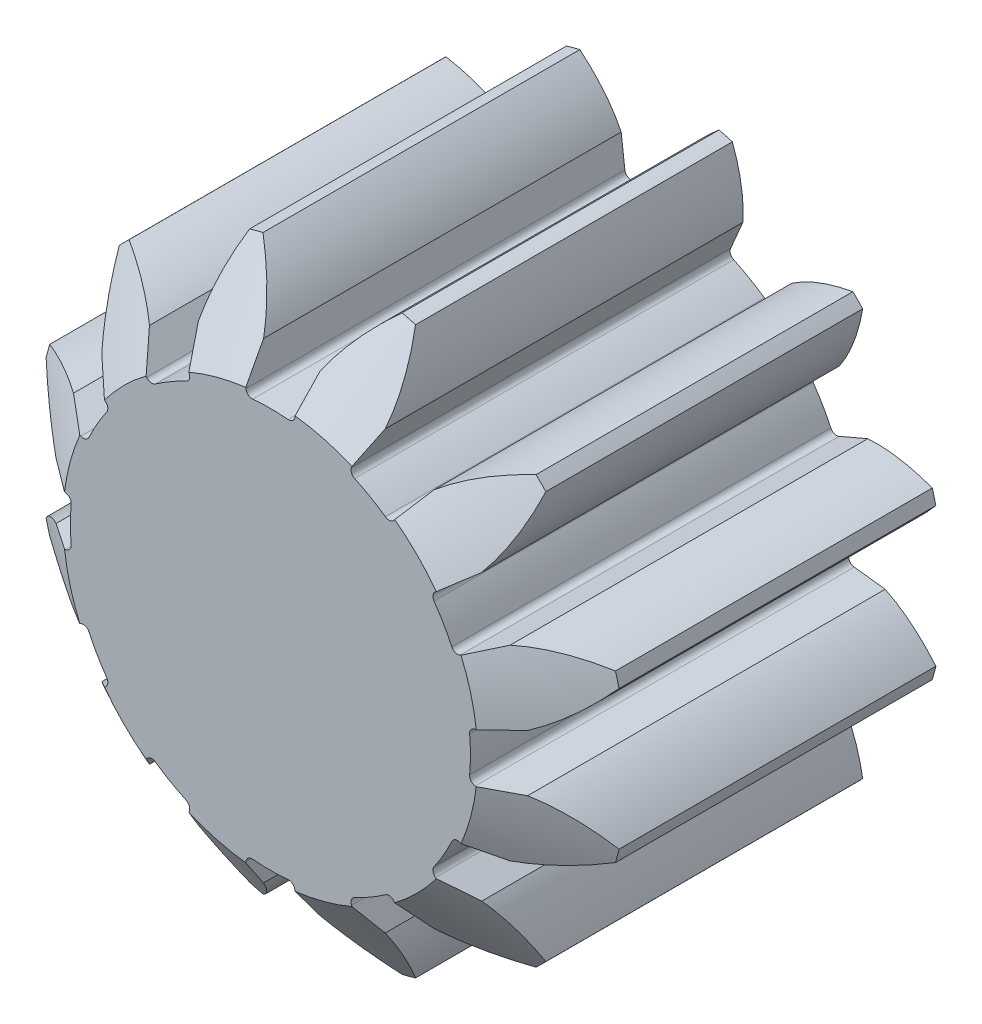
SolidWorks part; units mm, degrees
ref_plane "前视基准面" through (0, 0, 0) normal (0, 0, 1) x (1, 0, 0)
ref_plane "上视基准面" through (0, 0, 0) normal (0, 1, 0) x (1, 0, 0)
ref_plane "右视基准面" through (0, 0, 0) normal (1, 0, 0) x (0, 0, -1)
sketch "直齿轮" plane through (0, 0, 0) normal (0, 0, 1) x (1, 0, 0)
  line L0 (0, 14) -> (0, -14) construction
  line L1 (0, 0) -> (-1.3412, 11.1963)
  line L2 (0, 0) -> (1.3412, 11.1963)
  circle A0 centre (0, 0) radius 14
  arc A1 (1.5663, 11.8973) -> (-1.5663, 11.8973) centre (0, 0) ccw
  circle A2 centre (0, 0) radius 9.5
  circle A3 centre (0, 0) radius 11.2763
  spline S0 degree 4 poles (0.5104, 10.8373) (0.5087, 10.8802) (0.5014, 10.9656) (0.4731, 11.1267) (0.4127, 11.3596) (0.277, 11.753) (-0.0082, 12.3501) (-0.4967, 13.0965) (-1.3216, 14.0307) (-2.4412, 14.9688) (-3.8063, 15.812) (-5.3884, 16.5087) (-7.0436, 17.0043) (-8.7436, 17.3098) (-10.5508, 17.442) (-12.7938, 17.3717) (-15.4399, 16.9453) (-18.4103, 16.0061) (-21.5089, 14.4656) (-24.3525, 12.4965) (-26.9034, 10.1625) (-28.856, 7.8529) (-30.319, 5.7166) (-31.3943, 3.848) (-32.1672, 2.306) (-32.8522, 0.7235) (-33.449, -0.8951) (-34.0845, -2.9542) (-34.5731, -5.0569) (-34.8816, -6.9706) (-35.0445, -8.5826) (-35.1063, -9.4362) (-35.138, -10.019) (-35.1582, -10.475) (-35.1745, -11.1216) (-35.1793, -11.604) (-35.1756, -12.3979) (-35.1555, -13.0081) (-35.1236, -13.7549) (-35.0774, -14.4165) (-35.0185, -15.1311) (-34.9461, -15.8066) (-34.8823, -16.3369) (-34.8352, -16.674) (-34.8107, -16.8492) knots 0 0 0 0 0 0.002802 0.005604 0.010661 0.015718 0.02996 0.048734 0.068727 0.096889 0.125051 0.153212 0.181374 0.209535 0.237696 0.271429 0.327752 0.384075 0.440398 0.496721 0.553044 0.609367 0.637529 0.66569 0.693852 0.722013 0.750174 0.778336 0.834659 0.86282 0.876901 0.883942 0.890982 0.900036 0.909091 0.920455 0.931818 0.943182 0.954545 0.965909 0.977273 0.988636 1 1 1 1 1 construction
  spline S1 degree 4 poles (-1.3412, 11.1963) (-1.4143, 11.3505) (-1.6248, 11.7455) (-2.0413, 12.3619) (-2.8158, 13.2253) (-3.8997, 14.1193) (-5.2192, 14.9202) (-6.7463, 15.5786) (-8.3421, 16.0429) (-9.9797, 16.3241) (-11.7191, 16.4378) (-13.8762, 16.3534) (-16.4184, 15.9235) (-19.2687, 14.9979) (-22.2378, 13.4928) (-24.9584, 11.5775) (-27.3948, 9.3133) (-29.2558, 7.077) (-30.6471, 5.0111) (-31.6676, 3.2056) (-32.3996, 1.7166) (-33.0467, 0.1892) (-33.6086, -1.3723) (-34.2045, -3.3577) (-34.6589, -5.384) (-34.9413, -7.2271) (-35.086, -8.779) (-35.1391, -9.6005) (-35.1652, -10.1614) (-35.1812, -10.6002) (-35.1921, -11.2223) (-35.1931, -11.6864) (-35.1836, -12.45) (-35.1626, -12.9672) (-35.1409, -13.4074) (-35.1253, -13.6673) (-35.1196, -13.7558) knots 0.018362 0.018362 0.018362 0.018362 0.018362 0.02996 0.048734 0.068727 0.096889 0.125051 0.153212 0.181374 0.209535 0.237696 0.271429 0.327752 0.384075 0.440398 0.496721 0.553044 0.609367 0.637529 0.66569 0.693852 0.722013 0.750174 0.778336 0.834659 0.86282 0.876901 0.883942 0.890982 0.900036 0.909091 0.920455 0.931818 0.943182 0.949152 0.949152 0.949152 0.949152 0.949152
  spline S2 degree 4 poles (-0.5104, 10.8373) (-0.5087, 10.8802) (-0.5014, 10.9656) (-0.4731, 11.1267) (-0.4127, 11.3596) (-0.277, 11.753) (0.0082, 12.3501) (0.4967, 13.0965) (1.3216, 14.0307) (2.4412, 14.9688) (3.8063, 15.812) (5.3884, 16.5087) (7.0436, 17.0043) (8.7436, 17.3098) (10.5508, 17.442) (12.7938, 17.3717) (15.4399, 16.9453) (18.4103, 16.0061) (21.5089, 14.4656) (24.3525, 12.4965) (26.9034, 10.1625) (28.856, 7.8529) (30.319, 5.7166) (31.3943, 3.848) (32.1672, 2.306) (32.8522, 0.7235) (33.449, -0.8951) (34.0845, -2.9542) (34.5731, -5.0569) (34.8816, -6.9706) (35.0445, -8.5826) (35.1063, -9.4362) (35.138, -10.019) (35.1582, -10.475) (35.1745, -11.1216) (35.1793, -11.604) (35.1756, -12.3979) (35.1555, -13.0081) (35.1236, -13.7549) (35.0774, -14.4165) (35.0185, -15.1311) (34.9461, -15.8066) (34.8823, -16.3369) (34.8352, -16.674) (34.8107, -16.8492) knots 0 0 0 0 0 0.002802 0.005604 0.010661 0.015718 0.02996 0.048734 0.068727 0.096889 0.125051 0.153212 0.181374 0.209535 0.237696 0.271429 0.327752 0.384075 0.440398 0.496721 0.553044 0.609367 0.637529 0.66569 0.693852 0.722013 0.750174 0.778336 0.834659 0.86282 0.876901 0.883942 0.890982 0.900036 0.909091 0.920455 0.931818 0.943182 0.954545 0.965909 0.977273 0.988636 1 1 1 1 1 construction
  spline S3 degree 4 poles (1.3412, 11.1963) (1.4143, 11.3505) (1.6248, 11.7455) (2.0413, 12.3619) (2.8158, 13.2253) (3.8997, 14.1193) (5.2192, 14.9202) (6.7463, 15.5786) (8.3421, 16.0429) (9.9797, 16.3241) (11.7191, 16.4378) (13.8762, 16.3534) (16.4184, 15.9235) (19.2687, 14.9979) (22.2378, 13.4928) (24.9584, 11.5775) (27.3948, 9.3133) (29.2558, 7.077) (30.6471, 5.0111) (31.6676, 3.2056) (32.3996, 1.7166) (33.0467, 0.1892) (33.6086, -1.3723) (34.2045, -3.3577) (34.6589, -5.384) (34.9413, -7.2271) (35.086, -8.779) (35.1391, -9.6005) (35.1652, -10.1614) (35.1812, -10.6002) (35.1921, -11.2223) (35.1931, -11.6864) (35.1836, -12.45) (35.1626, -12.9672) (35.1409, -13.4074) (35.1253, -13.6673) (35.1196, -13.7558) knots 0.018362 0.018362 0.018362 0.018362 0.018362 0.02996 0.048734 0.068727 0.096889 0.125051 0.153212 0.181374 0.209535 0.237696 0.271429 0.327752 0.384075 0.440398 0.496721 0.553044 0.609367 0.637529 0.66569 0.693852 0.722013 0.750174 0.778336 0.834659 0.86282 0.876901 0.883942 0.890982 0.900036 0.909091 0.920455 0.931818 0.943182 0.949152 0.949152 0.949152 0.949152 0.949152
  dimension "齿顶圆" = 28
  dimension "分度圆" = 24
  dimension "齿根圆" = 19
  dimension "基圆直径" = 22.5526
  dimension "D1" = 3.1416
extrude "齿轮毛坯" add sketch "直齿轮" along normal mid plane 22 contours A0
chamfer "轮齿倒角" distance 1 angle 45 2 edges at (14, 0, -11) (14, 0, 11)
sketch "草图2" plane through (0, 0, 0) normal (0, 0, 1) x (1, 0, 0)
  line L0 (0, 0) -> (-1.3412, 11.1963) construction
  line L1 (0, 0) -> (1.3412, 11.1963) construction
  line L2 (0, 0) -> (-1.3412, 11.1963)
  line L3 (0, 0) -> (1.3412, 11.1963)
  circle A0 centre (0, 0) radius 14 construction
  circle A1 centre (0, 0) radius 14
  circle A2 centre (0, 0) radius 9.5 construction
  circle A3 centre (0, 0) radius 9.5
  spline S0 degree 4 poles (-1000.3168, -32.7859) (-34.8369, -15.4454) (0.1123, -1.0379) (1.6887, 8.2033) (-2.8158, 13.2253) (-3.8997, 14.1193) (-5.2192, 14.9202) (-6.7463, 15.5786) (-8.3421, 16.0429) (-9.9797, 16.3241) (-11.7191, 16.4378) (-13.8762, 16.3534) (-16.4184, 15.9235) (-19.2687, 14.9979) (-22.2378, 13.4928) (-24.9584, 11.5775) (-27.3948, 9.3133) (-29.2558, 7.077) (-30.6471, 5.0111) (-31.6676, 3.2056) (-32.3996, 1.7166) (-33.0467, 0.1892) (-33.6086, -1.3723) (-34.2045, -3.3577) (-34.6589, -5.384) (-34.9413, -7.2271) (-35.086, -8.779) (-35.1391, -9.6005) (-35.1652, -10.1614) (-35.1812, -10.6002) (-35.1921, -11.2223) (-35.1931, -11.6864) (-35.1836, -12.45) (-35.0654, -15.3572) (-34.587, -21.9927) (-33.6323, 18.5401) (-36.6239, -1013.6039) knots -0.359858 -0.359858 -0.359858 -0.359858 -0.359858 0.02996 0.048734 0.068727 0.096889 0.125051 0.153212 0.181374 0.209535 0.237696 0.271429 0.327752 0.384075 0.440398 0.496721 0.553044 0.609367 0.637529 0.66569 0.693852 0.722013 0.750174 0.778336 0.834659 0.86282 0.876901 0.883942 0.890982 0.900036 0.909091 0.920455 0.931818 0.943182 1.134286 1.134286 1.134286 1.134286 1.134286 only from (-1.3412, 11.1963) to (-35.1196, -13.7558) construction
  spline S1 degree 4 poles (-1.3412, 11.1963) (-1.4143, 11.3505) (-1.6248, 11.7455) (-2.0413, 12.3619) (-2.8158, 13.2253) (-3.8997, 14.1193) (-5.2192, 14.9202) (-6.7463, 15.5786) (-8.3421, 16.0429) (-9.9797, 16.3241) (-11.7191, 16.4378) (-13.8762, 16.3534) (-16.4184, 15.9235) (-19.2687, 14.9979) (-22.2378, 13.4928) (-24.9584, 11.5775) (-27.3948, 9.3133) (-29.2558, 7.077) (-30.6471, 5.0111) (-31.6676, 3.2056) (-32.3996, 1.7166) (-33.0467, 0.1892) (-33.6086, -1.3723) (-34.2045, -3.3577) (-34.6589, -5.384) (-34.9413, -7.2271) (-35.086, -8.779) (-35.1391, -9.6005) (-35.1652, -10.1614) (-35.1812, -10.6002) (-35.1921, -11.2223) (-35.1931, -11.6864) (-35.1836, -12.45) (-35.1626, -12.9672) (-35.1409, -13.4074) (-35.1253, -13.6673) (-35.1196, -13.7558) knots 0.018362 0.018362 0.018362 0.018362 0.018362 0.02996 0.048734 0.068727 0.096889 0.125051 0.153212 0.181374 0.209535 0.237696 0.271429 0.327752 0.384075 0.440398 0.496721 0.553044 0.609367 0.637529 0.66569 0.693852 0.722013 0.750174 0.778336 0.834659 0.86282 0.876901 0.883942 0.890982 0.900036 0.909091 0.920455 0.931818 0.943182 0.949152 0.949152 0.949152 0.949152 0.949152
  spline S2 degree 4 poles (1000.3168, -32.7859) (34.8369, -15.4454) (-0.1123, -1.0379) (-1.6887, 8.2033) (2.8158, 13.2253) (3.8997, 14.1193) (5.2192, 14.9202) (6.7463, 15.5786) (8.3421, 16.0429) (9.9797, 16.3241) (11.7191, 16.4378) (13.8762, 16.3534) (16.4184, 15.9235) (19.2687, 14.9979) (22.2378, 13.4928) (24.9584, 11.5775) (27.3948, 9.3133) (29.2558, 7.077) (30.6471, 5.0111) (31.6676, 3.2056) (32.3996, 1.7166) (33.0467, 0.1892) (33.6086, -1.3723) (34.2045, -3.3577) (34.6589, -5.384) (34.9413, -7.2271) (35.086, -8.779) (35.1391, -9.6005) (35.1652, -10.1614) (35.1812, -10.6002) (35.1921, -11.2223) (35.1931, -11.6864) (35.1836, -12.45) (35.0654, -15.3572) (34.587, -21.9927) (33.6323, 18.5401) (36.6239, -1013.6039) knots -0.359858 -0.359858 -0.359858 -0.359858 -0.359858 0.02996 0.048734 0.068727 0.096889 0.125051 0.153212 0.181374 0.209535 0.237696 0.271429 0.327752 0.384075 0.440398 0.496721 0.553044 0.609367 0.637529 0.66569 0.693852 0.722013 0.750174 0.778336 0.834659 0.86282 0.876901 0.883942 0.890982 0.900036 0.909091 0.920455 0.931818 0.943182 1.134286 1.134286 1.134286 1.134286 1.134286 only from (1.3412, 11.1963) to (35.1196, -13.7558) construction
  spline S3 degree 4 poles (1.3412, 11.1963) (1.4143, 11.3505) (1.6248, 11.7455) (2.0413, 12.3619) (2.8158, 13.2253) (3.8997, 14.1193) (5.2192, 14.9202) (6.7463, 15.5786) (8.3421, 16.0429) (9.9797, 16.3241) (11.7191, 16.4378) (13.8762, 16.3534) (16.4184, 15.9235) (19.2687, 14.9979) (22.2378, 13.4928) (24.9584, 11.5775) (27.3948, 9.3133) (29.2558, 7.077) (30.6471, 5.0111) (31.6676, 3.2056) (32.3996, 1.7166) (33.0467, 0.1892) (33.6086, -1.3723) (34.2045, -3.3577) (34.6589, -5.384) (34.9413, -7.2271) (35.086, -8.779) (35.1391, -9.6005) (35.1652, -10.1614) (35.1812, -10.6002) (35.1921, -11.2223) (35.1931, -11.6864) (35.1836, -12.45) (35.1626, -12.9672) (35.1409, -13.4074) (35.1253, -13.6673) (35.1196, -13.7558) knots 0.018362 0.018362 0.018362 0.018362 0.018362 0.02996 0.048734 0.068727 0.096889 0.125051 0.153212 0.181374 0.209535 0.237696 0.271429 0.327752 0.384075 0.440398 0.496721 0.553044 0.609367 0.637529 0.66569 0.693852 0.722013 0.750174 0.778336 0.834659 0.86282 0.876901 0.883942 0.890982 0.900036 0.909091 0.920455 0.931818 0.943182 0.949152 0.949152 0.949152 0.949152 0.949152
extrude "插齿" cut sketch "草图2" against normal mid plane 22 contours A3 S3 A1 S1 region at (0, 12.1328, 0)
fillet "圆角1" radius 0.3 2 edges at (1.1299, 9.4326, 0) (-1.1299, 9.4326, 0)
pattern_circular "圆周阵列1" count 12 over 360 about axis through (0, 0, 11) along (0, 0, -1) of "插齿", "圆角1"
fillet "圆角2" [suppressed] radius 0.3
pattern_circular "圆周阵列2" [suppressed] count 12 over 360 of bodies 102
pattern_circular "圆周阵列3" [suppressed] count 12 over 360 of bodies 102
sketch "分度圆" plane through (0, 0, 0) normal (0, 0, 1) x (1, 0, 0)
  circle A0 centre (0, 0) radius 12 construction
sketch "草图4" plane through (0, 0, -11) normal (0, 0, -1) x (-1, 0, 0)
  line L0 (-1.65, 2.2) -> (1.65, 2.2)
  circle A0 centre (0, 0) radius 2.75
  dimension "D1" = 5.5
  dimension "D2" = 2.2
extrude "切除-拉伸1" cut sketch "草图4" against normal blind 20 contours L0 A0 region at (0, -0.133, -11)
sketch "草图6" plane through (0, 0, 0) normal (1, 0, 0) x (0, 0, -1)
  line L0 (0, 0) -> (24.3439, 0) construction
  line L1 (-11, 9.8466) -> (-7.8, 14.3466)
  line L2 (-11, 12.274) -> (-11, 10.3668) construction
  line L3 (-7.8, 14.3466) -> (-11, 14.3466)
  line L4 (-11, 14.3466) -> (-11, 9.8466)
  dimension "D1" = 3.2
  dimension "D2" = 4.5
revolve "切除-旋转1" cut sketch "草图6" angle 360 about L0
sketch "草图7" plane through (0, 0, 11) normal (0, 0, 1) x (1, 0, 0)
  line L0 (1.65, 2.2) -> (-1.65, 2.2)
  arc A0 (1.65, 2.2) -> (-1.65, 2.2) centre (0, 0) ccw construction
  arc A1 (1.65, 2.2) -> (-1.65, 2.2) centre (0, 0) ccw
extrude "凸台-拉伸1" add sketch "草图7" against normal blind 4
sketch "草图9" plane through (0, 0, -11) normal (0, 0, -1) x (-1, 0, 0)
  circle A0 centre (0, 0) radius 30
  dimension "D1" = 60
extrude "切除-拉伸3" cut sketch "草图9" against normal blind 4
equation "\"m\"= 2'模数"
equation "\"z\"= 12'齿数"
equation "\"a\"= 20'压力角（常见为20°）"
equation "\"B\"= 22'齿宽"
equation "\"C1\"= 1'轮齿倒角（若设为0，则无倒角）"
equation "\"R\"= 0.3'齿根圆角（若设为0，则无圆角）"
equation "\"x\"= 0'变位系数"
equation "\"ha\"= 1'齿顶高系数"
equation "\"c\"= 0.25'顶隙系数"
equation "\"分度圆@直齿轮\"=\"m\" * \"z\""
equation "\"齿顶圆@直齿轮\" = \"m\" * ( \"z\" + 2 * ( \"ha\" + \"x\" ) )"
equation "\"齿根圆@直齿轮\" = \"m\" * ( \"z\" - 2 * ( \"ha\" - \"x\" + \"c\" ) )"
equation "\"基圆直径@直齿轮\"= \"m\" * \"z\" * cos ( \"a\" )"
equation "\"D1@直齿轮\"= \"m\" * ( pi / 2 ) - 2 * \"m\" * tan ( \"a\" ) * \"x\"'作者：机械菌-"
equation "\"圆周阵列3\"= IIF ( \"R\">0 , \"suppressed\" , \"unsuppressed\" )"
equation "\"圆角1\"=IIF ( \"R\">0 ,IIF ( \"m\" * ( \"z\" - 2 * ( \"ha\" - \"x\" + \"c\" ) ) < \"m\" * \"z\" * cos ( \"a\" ) , \"unsuppressed\" , \"suppressed\" ) , \"suppressed\" )"
equation "\"圆周阵列1\"=IIF ( \"R\">0 , IIF ( \"m\" * ( \"z\" - 2 * ( \"ha\" - \"x\" + \"c\" ) ) < \"m\" * \"z\" * cos ( \"a\" ) , \"unsuppressed\" , \"suppressed\" ), \"suppressed\" )"
equation "\"圆角2\"=IIF ( \"R\">0 ,IIF ( \"m\" * ( \"z\" - 2 * ( \"ha\" - \"x\" + \"c\" ) ) > \"m\" * \"z\" * cos ( \"a\" ) , \"unsuppressed\" , \"suppressed\" ) , \"suppressed\" )"
equation "\"圆周阵列2\"=IIF ( \"R\">0 , IIF ( \"m\" * ( \"z\" - 2 * ( \"ha\" - \"x\" + \"c\" ) ) > \"m\" * \"z\" * cos ( \"a\" ) , \"unsuppressed\" , \"suppressed\" ), \"suppressed\" )"
equation "\"轮齿倒角\"= IIF ( \"C1\" > 0 , \"unsuppressed\" , \"suppressed\" )"
